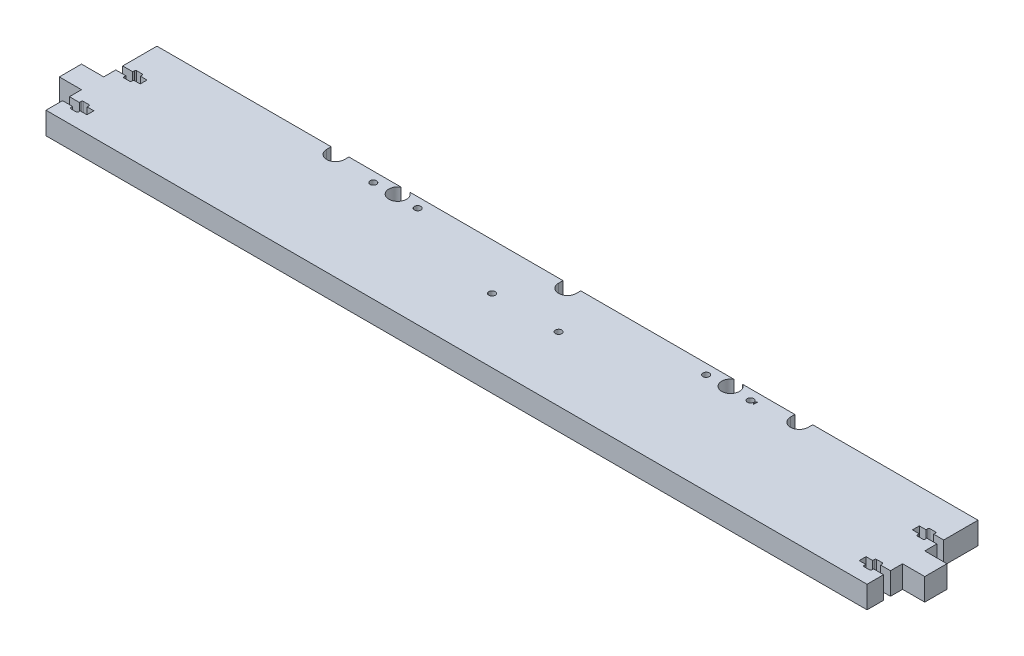
SolidWorks part; units mm, degrees
ref_plane "Front Plane" through (0, 0, 0) normal (0, 0, 1) x (1, 0, 0)
ref_plane "Top Plane" through (0, 0, 0) normal (0, 1, 0) x (1, 0, 0)
ref_plane "Right Plane" through (0, 0, 0) normal (1, 0, 0) x (0, 0, -1)
sketch "Sketch1" plane through (0, 0, 0) normal (0, 1, 0) x (1, 0, 0)
  line L0 (0, 25) -> (0, -25)
  line L1 (-185, 25) -> (0, 25)
  line L2 (-185, 25) -> (-185, -25) construction
  line L3 (-185, -25) -> (0, -25)
  line L4 (-185, -4) -> (-195, -4) construction
  line L5 (-185, 25) -> (0, 0) construction
  line L6 (-185, -25) -> (0, 0) construction
  line L7 (-185, -9) -> (-195, -9)
  line L8 (-195, -9) -> (-195, 1)
  line L9 (-195, 1) -> (-185, 1)
  line L10 (-185, 1) -> (-185, 25)
  line L11 (-185, -9) -> (-185, -25)
  line L47 (0, -25) -> (0, 25) construction
  line L89 (0, -25) -> (0, 25) construction
  point P0 (0, 0)
  dimension "D1" = 185
  dimension "D25" = 25
  dimension "D4" = 50
  dimension "D3" = 21
  dimension "D5" = 10
  dimension "D6" = 10
  dimension "D7" = 5
extrude "MainBody" add sketch "Sketch1" along normal blind 10 contours L3 region at (-93.5428, 0, 0.0428)
sketch "Sketch5" plane through (0, 10, 0) normal (0, 1, 0) x (1, 0, 0)
  line L0 (-185, 8) -> (-174, 8) construction
  line L1 (-185, 1) -> (-185, 25) construction
  line L2 (-185, 9.55) -> (-174, 9.55) construction
  line L3 (-174, 9.55) -> (-174, 6.45) construction
  line L4 (-174, 6.45) -> (-185, 6.45) construction
  line L5 (-185, 9.55) -> (-180.5, 9.55)
  line L6 (-180.5, 9.55) -> (-180.5, 10.35)
  line L7 (-180, 10.85) -> (-177.5, 10.85)
  line L8 (-177, 10.35) -> (-177, 9.55)
  line L9 (-177, 9.55) -> (-174, 9.55)
  line L10 (-174, 9.55) -> (-174, 6.45)
  line L11 (-185, 6.45) -> (-185, 9.55)
  line L12 (-195, -9) -> (-195, 1) construction
  line L13 (-185, 6.45) -> (-174, 6.45) construction
  line L14 (-177, 6.45) -> (-174, 6.45)
  line L15 (-177, 5.65) -> (-177, 6.45)
  line L16 (-180, 5.15) -> (-177.5, 5.15)
  line L17 (-180.5, 6.45) -> (-180.5, 5.65)
  line L18 (-185, 6.45) -> (-180.5, 6.45)
  line L19 (-185, 1) -> (-185, -9) construction
  line L20 (-195, -4) -> (-185, -4) construction
  line L21 (-195, -9) -> (-195, 1) construction
  line L22 (-185, -14.45) -> (-174, -14.45) construction
  line L23 (-174, -14.45) -> (-185, -14.45) construction
  line L24 (-174, -17.55) -> (-174, -14.45) construction
  line L25 (-185, -17.55) -> (-174, -17.55) construction
  line L26 (-185, -16) -> (-174, -16) construction
  line L27 (-185, -14.45) -> (-180.5, -14.45)
  line L28 (-180.5, -14.45) -> (-180.5, -13.65)
  line L29 (-180, -13.15) -> (-177.5, -13.15)
  line L30 (-177, -13.65) -> (-177, -14.45)
  line L31 (-177, -14.45) -> (-174, -14.45)
  line L32 (-185, -14.45) -> (-185, -17.55)
  line L33 (-174, -17.55) -> (-174, -14.45)
  line L34 (-177, -17.55) -> (-174, -17.55)
  line L35 (-177, -18.35) -> (-177, -17.55)
  line L36 (-180, -18.85) -> (-177.5, -18.85)
  line L37 (-180.5, -17.55) -> (-180.5, -18.35)
  line L38 (-185, -17.55) -> (-180.5, -17.55)
  line L39 (-185, 6.45) -> (-174, 6.45) construction
  arc A0 (-177.5, 10.85) -> (-177, 10.35) centre (-177.5, 10.35) cw
  arc A1 (-180.5, 10.35) -> (-180, 10.85) centre (-180, 10.35) cw
  arc A2 (-180.5, 5.65) -> (-180, 5.15) centre (-180, 5.65) ccw
  arc A3 (-177.5, 5.15) -> (-177, 5.65) centre (-177.5, 5.65) ccw
  arc A4 (-177.5, -13.15) -> (-177, -13.65) centre (-177.5, -13.65) cw
  arc A5 (-180.5, -13.65) -> (-180, -13.15) centre (-180, -13.65) cw
  arc A6 (-180.5, -18.35) -> (-180, -18.85) centre (-180, -18.35) ccw
  arc A7 (-177.5, -18.85) -> (-177, -18.35) centre (-177.5, -18.35) ccw
  point P6 (-195, -4)
  point P17 (-177, 10.85)
  point P20 (-180.5, 10.85)
  point P29 (-180.5, 5.15)
  point P30 (-177, 5.15)
  point P61 (-177, -13.15)
  point P62 (-180.5, -13.15)
  point P63 (-180.5, -18.85)
  point P64 (-177, -18.85)
  dimension "D8" = 0.5
  dimension "D1" = 11
  dimension "D2" = 1.55
  dimension "D4" = 3.5
  dimension "D5" = 8
  dimension "D6" = 2.85
  dimension "D7" = 12
extrude "ScrewCutouts" cut sketch "Sketch5" against normal through all
mirror "Mirror1" about plane through (0, 0, 0) normal (1, 0, 0) of "ScrewCutouts", "MainBody"
sketch "Sketch3" plane through (0, 10, 0) normal (0, 1, 0) x (1, 0, 0)
  line L0 (2, 25) -> (2, -25) construction
  line L1 (-185, 25) -> (185, 25) construction
  line L2 (-185, -25) -> (185, -25) construction
  line L3 (-63, 20.5) -> (-83, 20.5) construction
  line L4 (-73, 17.5) -> (-73, 25.5) construction
  line L5 (77, 17.5) -> (77, 25.5) construction
  line L6 (67, 20.5) -> (87, 20.5) construction
  circle A0 centre (-73, 21.5) radius 4
  circle A1 centre (-83, 20.5) radius 1.45
  circle A2 centre (-63, 20.5) radius 1.45
  circle A3 centre (67, 20.5) radius 1.45
  circle A4 centre (87, 20.5) radius 1.45
  circle A5 centre (77, 21.5) radius 4
  dimension "D2" = 8
  dimension "D4" = 2.9
  dimension "D1" = 3.5
  dimension "D5" = 75
  dimension "D6" = 2
  dimension "D3" = 10
  dimension "D7" = 1
extrude "RodCutouts" cut sketch "Sketch3" against normal through all
sketch "Sketch6" plane through (0, 10, 0) normal (0, 1, 0) x (1, 0, 0)
  line L0 (-73, 21.5) -> (77, 21.5) construction
  line L1 (2, 21.5) -> (2, -25) construction
  line L2 (-185, -25) -> (185, -25) construction
  line L3 (17, 4) -> (-13, 4) construction
  line L4 (-71.0635, 25) -> (75.0635, 25) construction
  circle A0 centre (-13, 4) radius 1.45
  circle A1 centre (17, 4) radius 1.45
  point P13 (2, 4)
  dimension "D3" = 21
  dimension "D1" = 2.9
  dimension "D2" = 15
extrude "Cut-Extrude1" cut sketch "Sketch6" against normal through all
sketch "Sketch7" plane through (0, 10, 0) normal (0, 1, 0) x (1, 0, 0)
  line L0 (-73, 21.5) -> (77, 21.5) construction
  line L1 (2, 21.5) -> (2, -25) construction
  line L3 (-102.5, 25) -> (-102.5, 23) construction
  line L4 (-185, 25) -> (-74.9365, 25) construction
  line L5 (-98.5, 25) -> (-98.5, 23)
  line L6 (-106.5, 25) -> (-106.5, 23)
  line L7 (106.5, 25) -> (106.5, 23) construction
  line L8 (102.5, 25) -> (102.5, 23)
  line L9 (110.5, 25) -> (110.5, 23)
  line L12 (-185, -25) -> (185, -25) construction
  arc A0 (-98.5, 25) -> (-106.5, 25) centre (-102.5, 25) ccw
  arc A1 (-106.5, 23) -> (-98.5, 23) centre (-102.5, 23) ccw
  arc A2 (102.5, 25) -> (110.5, 25) centre (106.5, 25) cw
  arc A3 (110.5, 23) -> (102.5, 23) centre (106.5, 23) cw
  point P12 (-102.5, 24)
  point P19 (106.5, 24)
  dimension "D1" = 4
  dimension "D2" = 2
  dimension "D3" = 104.5
extrude "BedAdjustmentScrewCutout" cut sketch "Sketch7" against normal through all
sketch "Sketch8" plane through (0, 10, 0) normal (0, 1, 0) x (1, 0, 0)
  line L0 (88.25, 20.5) -> (89.25, 20.5) construction
  line L1 (88.45, 20.5) -> (88.45, 25) construction
  line L2 (88.25, 20.5) -> (89.25, 21.5)
  line L3 (89.25, 21.5) -> (89.25, 19.5)
  line L4 (88.25, 20.5) -> (89.25, 19.5)
  line L5 (78.9365, 25) -> (102.5, 25) construction
  circle A1 centre (87, 20.5) radius 1.45 construction
  point P9 (89.25, 20.5)
  dimension "D1" = 1
  dimension "D2" = 1
  dimension "D3" = 0.2
extrude "DirectionKey" cut sketch "Sketch8" against normal through all
sketch "Sketch9" plane through (0, 10, 0) normal (0, 1, 0) x (1, 0, 0)
  line L0 (-13, 4) -> (17, 4) construction
  line L1 (2, 4) -> (2, 25) construction
  line L2 (-71.0635, 25) -> (75.0635, 25) construction
  line L3 (2, 27) -> (2, 23) construction
  line L4 (6, 27) -> (6, 23)
  line L5 (-2, 27) -> (-2, 23)
  arc A0 (6, 27) -> (-2, 27) centre (2, 27) ccw
  arc A1 (-2, 23) -> (6, 23) centre (2, 23) ccw
  point P10 (2, 25)
  dimension "D1" = 4
  dimension "D2" = 2
extrude "Cut-Extrude2" cut sketch "Sketch9" against normal through all
equation "\"Y-ROD-SPACING\"=75"
equation "\"Y-BED-OFFSET\"=2"
equation "\"T-SLOT-NUT-FILLET-RADIUS\"=0.5"
equation "\"T-SLOT-SCREW-SHAFT-RADIUS\"=1.55"
equation "\"T-SLOT-SCREW-SHAFT-CUTOUT-LENGTH\"=11.0"
equation "\"T-SLOT-NUT-DEPTH\"=3.5"
equation "\"T-SLOT-NUT-WIDTH\"=2.85"
equation "\"T-SLOT-NUT-END-DISTANCE\"=8"
equation "\"ACRYLIC-TAB-CUTOUT-SIZE\"=\"ACRYLIC-THICKNESS\"+\"ACRYLIC-TAB-TOLERANCE\"*2"
equation "\"ACRYLIC-M3-HOLE\"=2.9"
equation "\"D1@Sketch5\"=\"T-SLOT-SCREW-SHAFT-CUTOUT-LENGTH\""
equation "\"D2@Sketch5\"=\"T-SLOT-SCREW-SHAFT-RADIUS\""
equation "\"D4@Sketch5\"=\"T-SLOT-NUT-DEPTH\""
equation "\"D5@Sketch5\"=\"T-SLOT-NUT-END-DISTANCE\""
equation "\"D6@Sketch5\"=\"T-SLOT-NUT-WIDTH\""
equation "\"D8@Sketch5\"=\"T-SLOT-NUT-FILLET-RADIUS\""
equation "\"D4@Sketch3\"=\"ACRYLIC-M3-HOLE\""
equation "\"D5@Sketch3\"=\"Y-ROD-SPACING\""
equation "\"D6@Sketch3\"=\"Y-BED-OFFSET\""
equation "\"Y-BED-ROD-INSET\"=3.5"
equation "\"D1@Sketch3\"=\"Y-BED-ROD-INSET\""
equation "\"SMOOTHROD-CAP-SCREW-DISTANCE\"=20"
equation "\"D3@Sketch3\"=\"SMOOTHROD-CAP-SCREW-DISTANCE\"/2"
equation "\"ACRYLIC-TAB-WIDTH\"=\"ACRYLIC-THICKNESS\""
equation "\"FRAME-WIDTH-INNER\"=370"
equation "\"D6@Sketch1\"=\"ACRYLIC-TAB-WIDTH\""
equation "\"D5@Sketch1\"=\"ACRYLIC-TAB-WIDTH\""
equation "\"D1@Sketch1\"=\"FRAME-WIDTH-INNER\"/2"
equation "\"X-ROD-SPACING\"=45"
equation "\"Z-ROD-SPACING\"=17.5"
equation "\"ACRYLIC-THICKNESS\"=10"
equation "\"ACRYLIC-THICKNESS2\"=4.5"
equation "\"NEMA17-HOLE-SPACING\"=31"
equation "\"NEMA17-CENTRAL-CUTOUT\"=22.5"
equation "\"Z-BRACKET-REACH\"=55"
equation "\"TOP-BRACKET-SPACING\"=40"
equation "\"SMOOTHROD-X-LENGTH\"=350"
equation "\"SMOOTHROD-Y-LENGTH\"=350"
equation "\"SMOOTHROD-Z-LENGTH\"=350"
equation "\"SMOOTHROD-TIGHTENING-HEADROOM\"=.25"
equation "\"LEADSCREW-Z-LENGTH\"=300"
equation "\"SCREW-LENGTH-FRAME\"=\"ACRYLIC-THICKNESS\" + 10"
equation "\"SCREW-HEAD-RADIUS\"=6"
equation "\"PRINTED-X-SMOOTHROD-DIAMETER\"=9.0"
equation "\"PRINTED-X-SMOOTHROD-CUTOUT\"=10"
equation "\"PRINTED-X-BASE-HEIGHT\"=10"
equation "\"PRINTED-LM8UU-CUTOUT-SIZE\"=15.5"
equation "\"PRINTED-LM8UU-CUTOUT-LENGTH\"=24.5"
equation "\"PRINTED-X-IDLER-HEIGHT\"=16"
equation "\"PSU-MOUNTING-WIDTH\"=95"
equation "\"PSU-MOUNTING-HEIGHT\"=177"
equation "\"D1@MainBody\"=\"ACRYLIC-THICKNESS\""
equation "\"D7@Sketch1\"=\"ACRYLIC-TAB-WIDTH\"/2"
equation "\"D1@Sketch6\"=\"ACRYLIC-M3-HOLE\""
equation "\"Y-BELT-TO-ROD-DISTANCE\"=20"
equation "\"Y-BED-SCREW-SPACING\"=209"
equation "\"Z-ROD-INSET\"=16"
equation "\"SPOOL-HOLDER-ROD-SPACING\"=150"
equation "\"D3@Sketch7\"=\"Y-BED-SCREW-SPACING\"/2"
equation "\"Y-BED-SCREW-CUTOUT-SLOT-HEIGHT\"=2"
equation "\"D2@Sketch7\"=\"Y-BED-SCREW-CUTOUT-SLOT-HEIGHT\""
equation "\"ACRYLIC-TAB-TOLERANCE\"=-.05"
equation "\"SCREW-LENGTH-MOTOR\"=\"ACRYLIC-THICKNESS\" + 5"
equation "\"SCREW-LENGTH-EXTRUDER\"=28"
equation "\"PRINTED-M3-HOLE\"=3.5"
equation "\"ACRYLIC-X-CARRIAGE-WIDTH\"=55"
equation "\"ACRYLIC-X-CARRIAGE-HEIGHT\"=75"
equation "\"ACRYLIC-X-CARRIAGE-LM8UU-CUTOUT-WIDTH\"=24.25"
equation "\"ACRYLIC-X-CARRIAGE-LM8UU-CUTOUT-HEIGHT\"=11.0"
equation "\"ACRYLIC-X-CARRIAGE-SCREW-SPACING-X\"=15"
equation "\"ACRYLIC-X-CARRIAGE-SCREW-SPACING-Y\"=33"
equation "\"ACRYLIC-X-CARRIAGE-CENTER-TAB-SPACING\"=14"
equation "\"ACRYLIC-X-CARRIAGE-EXTRUDER-OFFSET\"=26"
equation "\"ACRYLIC-X-CARRIAGE-EXTRUDER-ANGLE\"=90"
equation "\"ACRYLIC-X-CARRIAGE-EXTRUDER-SHELF-DEPTH\"=\"ACRYLIC-X-CARRIAGE-EXTRUDER-OFFSET\" + 28"
equation "\"ACRYLIC-X-CARRIAGE-EXTRUDER-BRACE-SPACING\"=23"
equation "\"ACRYLIC-X-CARRIAGE-EXTRUDER-BRACE-TAB-OFFSET\"=20"
equation "\"ACRYLIC-X-CARRIAGE-EXTRUDER-BRACE-HEIGHT\"=35"
equation "\"ACRYLIC-X-CARRIAGE-EXTRUDER-BRACE-SCREW-SPACING\"=22"
equation "\"ACRYLIC-X-CARRIAGE-DUAL-WIDTH-MULTIPLIER\"=1.65"
equation "\"ACRYLIC-X-CARRIAGE-DUAL-HOTEND-SPACING\"=42"
equation "\"ACRYLIC-X-CARRIAGE-DUAL-WIDTH\"=75"
equation "\"ACRYLIC-X-CARRIAGE-DUAL-HOTEND-SEPARATION\"=36"
equation "\"ACRYLIC-X-CARRIAGE-DUAL-MOUNT-PLATE-DEPTH\"=75"
equation "\"ACRYLIC-X-CARRIAGE-DUAL-MOUNT-BRACE-WIDTH\"=33"
equation "\"ACRYLIC-X-CARRIAGE-DUAL-MOUNT-SCREW-WIDTH\"=40"
equation "\"BLOWER-FAN-WIDTH\"=15"
equation "\"D2@Sketch9\"=\"Y-BED-SCREW-CUTOUT-SLOT-HEIGHT\""
